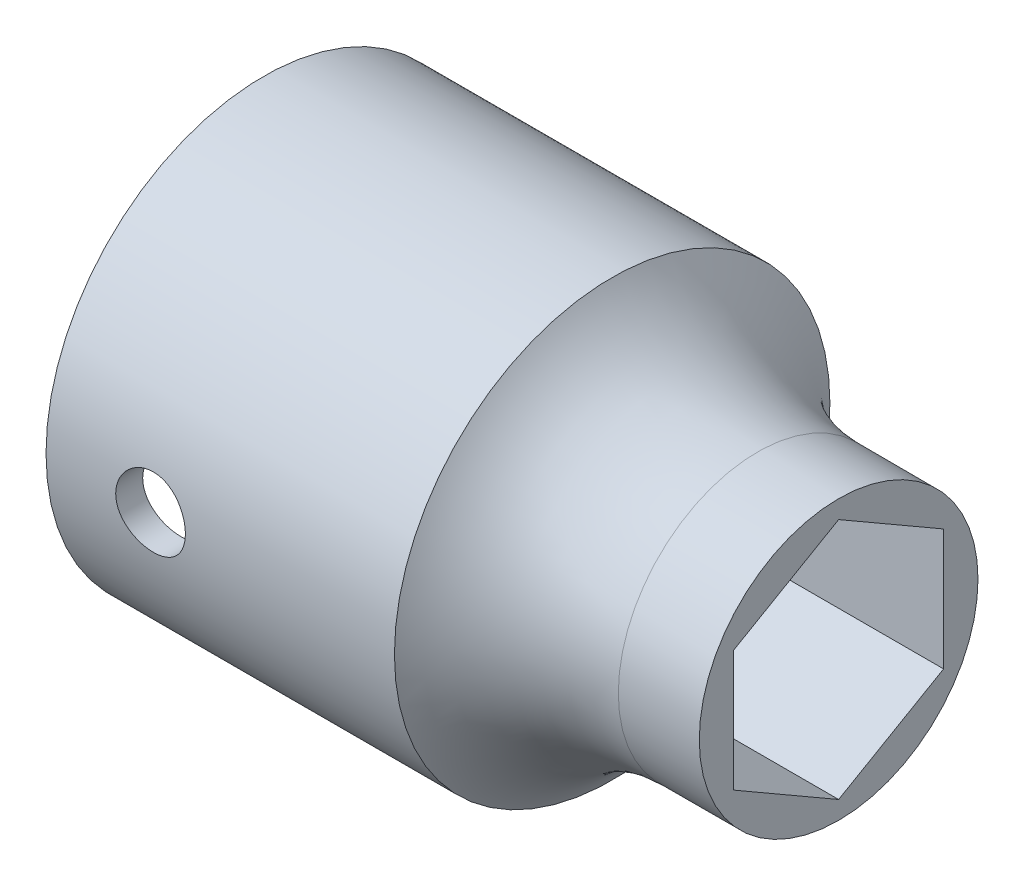
SolidWorks part; units mm, degrees
ref_plane "Alzado" through (0, 0, 0) normal (0, 0, 1) x (1, 0, 0)
ref_plane "Planta" through (0, 0, 0) normal (0, 1, 0) x (1, 0, 0)
ref_plane "Vista lateral" through (0, 0, 0) normal (1, 0, 0) x (0, 0, -1)
sketch "Croquis1" plane through (0, 0, 0) normal (1, 0, 0) x (0, 0, -1)
  line L1 (0, -6.9282) -> (6, -3.4641) construction
  line L2 (6, -3.4641) -> (6, 3.4641) construction
  line L3 (6, 3.4641) -> (0, 6.9282) construction
  line L4 (0, 6.9282) -> (-6, 3.4641) construction
  line L5 (-6, 3.4641) -> (-6, -3.4641) construction
  line L6 (-6, -3.4641) -> (0, -6.9282) construction
  circle A0 centre (0, 0) radius 6.4 construction
  circle A1 centre (0, 0) radius 6 construction
  circle A2 centre (0, 0) radius 8
  point P11 (0, 0)
  dimension "D2" = 12.8
  dimension "D3" = 16
  dimension "D1" = 12
extrude "Saliente-Extruir1" add sketch "Croquis1" along normal blind 30
sketch "Croquis2" plane through (30, 0, 0) normal (1, 0, 0) x (0, 0, -1)
  line L1 (0, -6.9571) -> (6.025, -3.4785)
  line L2 (6.025, -3.4785) -> (6.025, 3.4785)
  line L3 (6.025, 3.4785) -> (0, 6.9571)
  line L4 (0, 6.9571) -> (-6.025, 3.4785)
  line L5 (-6.025, 3.4785) -> (-6.025, -3.4785)
  line L6 (-6.025, -3.4785) -> (0, -6.9571)
  circle A0 centre (0, 0) radius 6.025 construction
  dimension "D1" = 12.05
extrude "Cortar-Extruir1" cut sketch "Croquis2" against normal blind 8.5
sketch "Croquis9" plane through (0, 0, 0) normal (-1, 0, 0) x (0, 0, 1)
  circle A0 centre (0, 0) radius 12.5
  dimension "D1" = 25
extrude "Saliente-Extruir5" add sketch "Croquis9" against normal blind 20
sketch "Croquis3" plane through (0, 0, 0) normal (-1, 0, 0) x (0, 0, 1)
  circle A0 centre (0, 0) radius 10.95
  dimension "D1" = 21.9
extrude "Cortar-Extruir2" cut sketch "Croquis3" against normal blind 19
sketch "Croquis4" plane through (19, 0, 0) normal (-1, 0, 0) x (0, 0, 1)
  circle A0 centre (0, 0) radius 2.025
  dimension "D1" = 4.05
extrude "Cortar-Extruir3" cut sketch "Croquis4" against normal up to next
sketch "Croquis5" plane through (0, 0, 0) normal (0, 0, 1) x (1, 0, 0)
  circle A0 centre (6, 0) radius 2
  dimension "D1" = 4
  dimension "D2" = 6
extrude "Cortar-Extruir4" cut sketch "Croquis5" against normal through all and the other way through all
sketch "Croquis7" plane through (30, 0, 0) normal (1, 0, 0) x (0, 0, -1)
  line L2 (-6.025, -3.4785) -> (0, -6.9571)
  line L8 (-6.025, -3.4785) -> (0, -6.9571)
  line L9 (6.025, 3.4785) -> (0, 6.9571)
  line L10 (0, -6.9571) -> (6.025, -3.4785)
  line L11 (0, -6.9571) -> (6.025, -3.4785)
  line L15 (6.025, 3.4785) -> (0, 6.9571)
  line L18 (6.025, -3.4785) -> (6.025, 3.4785)
  line L19 (6.025, -3.4785) -> (6.025, 3.4785)
  line L20 (0, 6.9571) -> (-6.025, 3.4785)
  line L21 (0, 6.9571) -> (-6.025, 3.4785)
  line L22 (-6.025, 3.4785) -> (-6.025, -3.4785)
  line L23 (-6.025, 3.4785) -> (-6.025, -3.4785)
  circle A0 centre (0, 0) radius 8 construction
  circle A1 centre (0, 0) radius 8
  dimension "D1" = 0
extrude "Saliente-Extruir3" add sketch "Croquis7" along normal blind 3
fillet "Redondeo1" radius 10 1 edges at (20, 0, 8)
equation "\"D1@Croquis2\"=12+0.05"
equation "\"D1@Croquis3\"=21.2+0.7"
